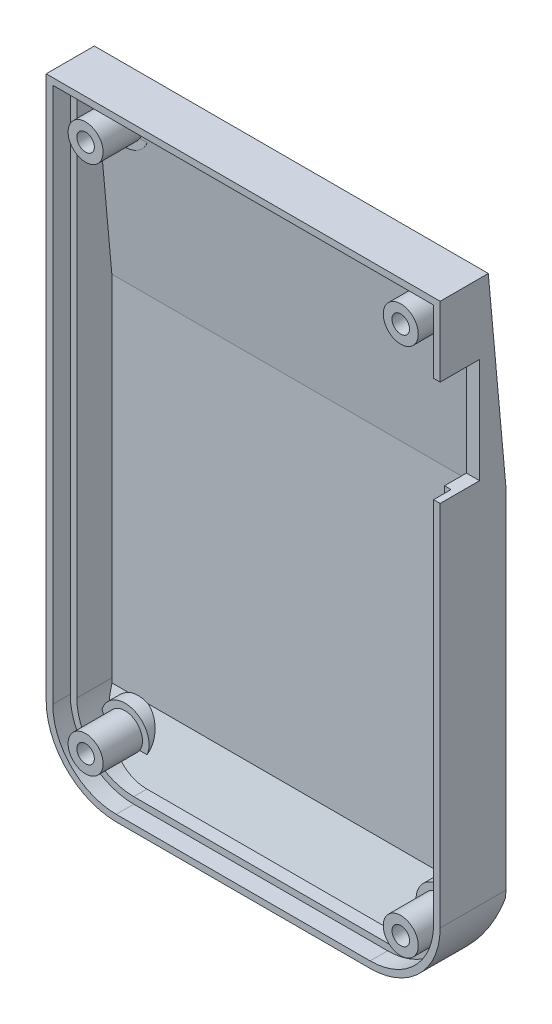
SolidWorks part; units mm, degrees
ref_plane "前视基准面" through (0, 0, 0) normal (0, 0, 1) x (1, 0, 0)
ref_plane "上视基准面" through (0, 0, 0) normal (0, 1, 0) x (1, 0, 0)
ref_plane "右视基准面" through (0, 0, 0) normal (1, 0, 0) x (0, 0, -1)
sketch "草图1" plane through (0, 0, 0) normal (0, 0, 1) x (1, 0, 0)
  line L1 (-45, 70) -> (0, 70)
  line L2 (-45, 70) -> (-45, 8)
  line L3 (-37, 0) -> (-8, 0)
  line L4 (0, 70) -> (0, 8)
  arc A0 (-8, 0) -> (0, 8) centre (-8, 8) ccw
  arc A1 (-45, 8) -> (-37, 0) centre (-37, 8) ccw
  point P8 (0, 0)
  point P11 (-45, 0)
  dimension "D3" = 8
  dimension "D1" = 45
  dimension "D2" = 70
extrude "凸台-拉伸1" add sketch "草图1" along normal blind 7.5 contours L1 L4 A0 L3 A1 L2
sketch "草图2" plane through (0, 0, 0) normal (1, 0, 0) x (0, 0, -1)
  line L0 (0, 0) -> (0, 7.2)
  line L1 (0, 0) -> (0, 8) construction
  line L2 (0, 7.2) -> (-3, 0)
  line L3 (-7.5, 0) -> (0, 0) construction
  line L4 (-3, 0) -> (0, 0)
  line L5 (0, 70) -> (-2, 70)
  line L6 (-7.5, 70) -> (0, 70) construction
  line L7 (-2, 70) -> (0, 48)
  line L8 (0, 70) -> (0, 8) construction
  line L9 (0, 48) -> (0, 70)
  dimension "D1" = 3
  dimension "D2" = 7.2
  dimension "D3" = 22
  dimension "D4" = 2
extrude "切除-拉伸1" cut sketch "草图2" against normal through all
shell "抽壳1" thickness 1.5 removed face at (-22.5, 25.4477, 7.5)
sketch "草图3" plane through (0, 0, 7.5) normal (0, 0, 1) x (1, 0, 0)
  line L0 (-37, 1.5) -> (-8, 1.5) construction
  line L1 (-43.5, 68.5) -> (-1.5, 68.5)
  line L2 (-43.5, 68.5) -> (-43.5, 8)
  line L3 (-37, 1.5) -> (-8, 1.5)
  line L4 (-1.5, 68.5) -> (-1.5, 8)
  line L5 (-1.5, 68.5) -> (-1.5, 8) construction
  line L6 (-44.25, 69.25) -> (-0.75, 69.25)
  line L7 (-0.75, 69.25) -> (-0.75, 8)
  line L8 (-37, 0.75) -> (-8, 0.75)
  line L9 (-44.25, 69.25) -> (-44.25, 8)
  arc A0 (-8, 1.5) -> (-1.5, 8) centre (-8, 8) ccw
  arc A1 (-43.5, 8) -> (-37, 1.5) centre (-37, 8) ccw
  arc A2 (-8, 0.75) -> (-0.75, 8) centre (-8, 8) ccw
  arc A3 (-44.25, 8) -> (-37, 0.75) centre (-37, 8) ccw
  dimension "D1" = 6.5
  dimension "D2" = 0.75
extrude "切除-拉伸2" cut sketch "草图3" against normal blind 2
sketch "草图4" plane through (0, 0, 1.5) normal (0, 0, 1) x (1, 0, 0)
  line L0 (-45, 70) -> (-45, 8) construction
  line L1 (-45, 70) -> (0, 70) construction
  line L2 (-22.5, -924.2136) -> (-22.5, 49075.7864) construction
  line L3 (-45, 48) -> (-45, 8) construction
  line L4 (0, 48) -> (0, 8) construction
  circle A0 centre (-40.5, 65.5) radius 2.75
  circle A1 centre (-40.5, 5) radius 2.75
  circle A2 centre (-4.5, 5) radius 2.75
  circle A3 centre (-4.5, 65.5) radius 2.75
  dimension "D3" = 5.5
  dimension "D1" = 4.5
  dimension "D2" = 4.5
  dimension "D5" = 60.5
  dimension "D4" = 2
extrude "凸台-拉伸2" add sketch "草图4" along normal blind 1.5
sketch "草图5" plane through (0, 0, 3) normal (0, 0, 1) x (1, 0, 0)
  circle A0 centre (-40.5, 65.5) radius 2
  circle A1 centre (-4.5, 65.5) radius 2
  circle A2 centre (-40.5, 5) radius 2
  circle A3 centre (-4.5, 5) radius 2
  arc A4 (-1.8757, 5.8221) -> (-7.0204, 3.9) centre (-4.5, 5) ccw construction
  dimension "D1" = 4
extrude "凸台-拉伸3" add sketch "草图5" along normal blind 4.5
sketch "草图6" plane through (0, 0, 0) normal (0, 0, -1) x (-1, 0, 0)
  circle A0 centre (4.5, 65.5) radius 1.75
  circle A1 centre (40.5, 65.5) radius 1.75
  circle A2 centre (40.5, 5) radius 1.75
  circle A3 centre (4.5, 5) radius 1.75
  circle A4 centre (4.5, 65.5) radius 2.75 construction
  circle A5 centre (40.5, 65.5) radius 2.75 construction
  arc A6 (43.1243, 5.8221) -> (37.9796, 3.9) centre (40.5, 5) ccw construction
  arc A7 (7.0204, 3.9) -> (1.8757, 5.8221) centre (4.5, 5) ccw construction
  dimension "D1" = 3.5
extrude "切除-拉伸3" cut sketch "草图6" against normal blind 2
sketch "草图9" plane through (0, 0, 0) normal (0, 0, 1) x (1, 0, 0)
  circle A0 centre (-40.5, 65.5) radius 1
  circle A1 centre (-4.5, 65.5) radius 1
  circle A2 centre (-4.5, 5) radius 1
  circle A3 centre (-40.5, 5) radius 1
  circle A8 centre (-4.5, 65.5) radius 1.75 construction
  circle A9 centre (-40.5, 65.5) radius 1.75 construction
  arc A10 (-39.45, 3.6) -> (-41.55, 3.6) centre (-40.5, 5) ccw construction
  arc A11 (-3.45, 3.6) -> (-5.55, 3.6) centre (-4.5, 5) ccw construction
  dimension "D1" = 2
extrude "切除-拉伸4" cut sketch "草图9" along normal through all
sketch "草图12" plane through (0, 0, 7.5) normal (0, 0, 1) x (1, 0, 0)
  line L0 (0, 70) -> (0, 8) construction
  line L1 (0, 62) -> (-1.5, 62)
  line L2 (0, 62) -> (0, 50)
  line L3 (0, 50) -> (-1.5, 50)
  line L4 (-1.5, 62) -> (-1.5, 50)
  line L5 (-1.5, 8) -> (-1.5, 68.5) construction
  line L6 (-45, 70) -> (0, 70) construction
  dimension "D1" = 8
  dimension "D2" = 12
extrude "切除-拉伸6" cut sketch "草图12" against normal blind 4.5
extrude "切除-拉伸7" cut sketch "草图2<3>" against normal through all
sketch "草图2<3>" plane through (0, 0, 0) normal (1, 0, 0) x (0, 0, -1) same geometry as "草图2"
sketch "草图13" plane through (0, 0, 0) normal (0, 0, -1) x (-1, 0, 0)
  line L0 (22.5, -949.9113) -> (22.5, 49050.0887) construction
  line L1 (7.5, 43) -> (37.5, 43)
  line L2 (7.5, 43) -> (7.5, 18)
  line L3 (7.5, 18) -> (37.5, 18)
  line L4 (37.5, 43) -> (37.5, 18)
  line L5 (0, 48) -> (0, 8) construction
  line L6 (45, 48) -> (45, 8) construction
  line L7 (45, 48) -> (0, 48) construction
  dimension "D1" = 30
  dimension "D2" = 25
  dimension "D3" = 5
extrude "切除-拉伸8" cut sketch "草图13" against normal blind 0.5
